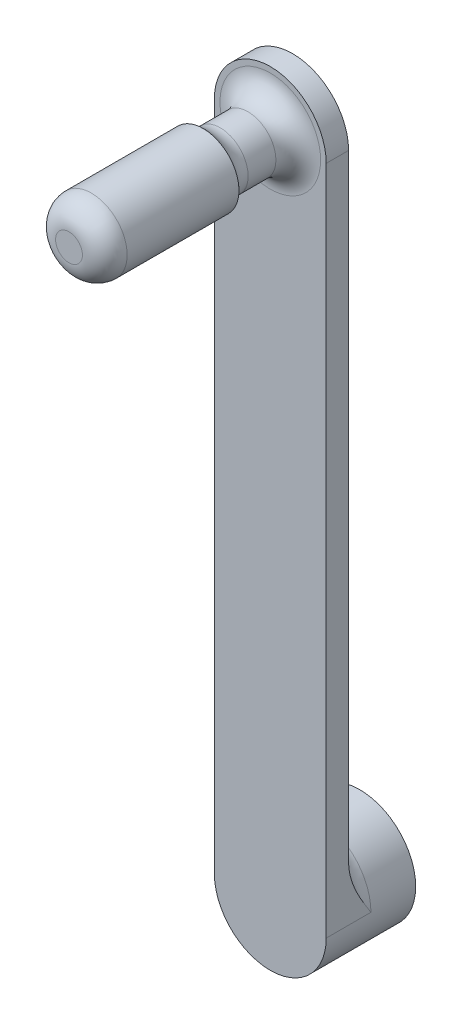
SolidWorks part; units mm, degrees
ref_plane "Front Plane" through (0, 0, 0) normal (0, 0, 1) x (1, 0, 0)
ref_plane "Top Plane" through (0, 0, 0) normal (0, 1, 0) x (1, 0, 0)
ref_plane "Right Plane" through (0, 0, 0) normal (1, 0, 0) x (0, 0, -1)
sketch "Sketch2" plane through (0, 0, 0) normal (0, 0, 1) x (1, 0, 0)
  circle A0 centre (0, 0) radius 15
  circle A1 centre (0, 0) radius 25
  dimension "D1" = 30
  dimension "D2" = 50
extrude "Boss-Extrude1" add sketch "Sketch2" along normal mid plane 30
sketch "Sketch3" plane through (0, 0, 15) normal (0, 0, 1) x (1, 0, 0)
  line L0 (0, 300) -> (0, 0) construction
  line L1 (25, 300) -> (25, 0)
  line L2 (-25, 300) -> (-25, 0)
  arc A0 (25, 300) -> (-25, 300) centre (0, 300) ccw
  arc A1 (-25, 0) -> (25, 0) centre (0, 0) ccw
  circle A2 centre (0, 0) radius 25 construction
  point P3 (0, 150)
  dimension "D1" = 300
extrude "Boss-Extrude2" add sketch "Sketch3" along normal blind 10
sketch "Sketch4" plane through (0, 0, -15) normal (0, 0, -1) x (-1, 0, 0)
  line L0 (0, 33) -> (0, -33) construction
  line L1 (-5, 19.5) -> (5, 19.5)
  line L2 (-5, 19.5) -> (-5, 10.5)
  line L3 (-5, 10.5) -> (5, 10.5)
  line L4 (5, 19.5) -> (5, 10.5)
  line L5 (-5, 19.5) -> (5, 10.5) construction
  line L6 (-5, 10.5) -> (5, 19.5) construction
  circle A0 centre (0, 0) radius 15 construction
  point P0 (0, 15)
  dimension "D1" = 10
  dimension "D2" = 9
extrude "Cut-Extrude1" cut sketch "Sketch4" against normal blind 20
fillet "Fillet1" radius 10 1 edges at (0, 25, 15)
sketch "Sketch7" plane through (0, 0, 0) normal (1, 0, 0) x (0, 0, -1)
  line L0 (-25, 300) -> (-115, 300) construction
  line L1 (-25, 312.5) -> (-47.4007, 312.5)
  line L2 (-55, 316) -> (-115, 316)
  line L3 (-115, 316) -> (-115, 300)
  line L4 (-25, 312.5) -> (-25, 300)
  line L5 (-25, 300) -> (-115, 300)
  arc A0 (-47.4007, 312.5) -> (-55, 316) centre (-47.4007, 322.5) cw
  dimension "D1" = 12.5
  dimension "D2" = 10
  dimension "D3" = 60
  dimension "D4" = 90
  dimension "D5" = 16
revolve "Revolve2" add sketch "Sketch7" angle 360 about L0
fillet "Fillet3" radius 10 2 edges at (-16, 300, 115) (12.5, 300, 25)
